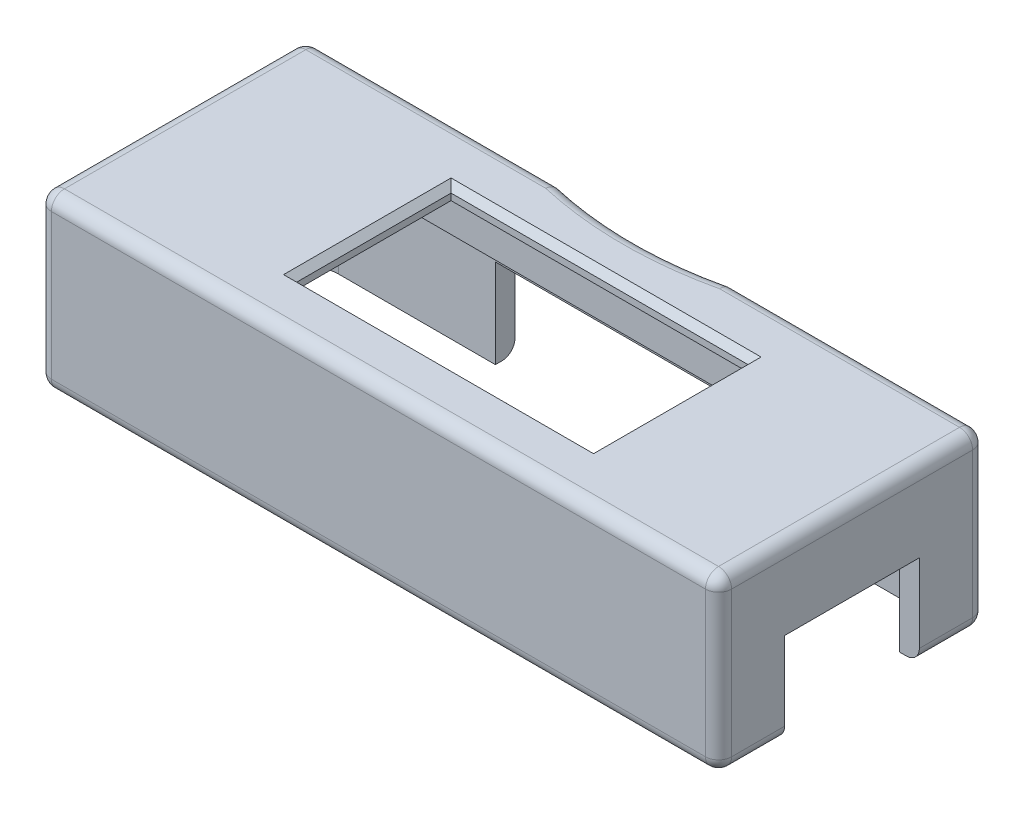
SolidWorks part; units mm, degrees
ref_plane "前视基准面" through (0, 0, 0) normal (0, 0, 1) x (1, 0, 0)
ref_plane "上视基准面" through (0, 0, 0) normal (0, 1, 0) x (1, 0, 0)
ref_plane "右视基准面" through (0, 0, 0) normal (1, 0, 0) x (0, 0, -1)
sketch "草图2" plane through (0, 0, 0) normal (0, 1, 0) x (1, 0, 0)
  line L0 (0.0138, 20.4331) -> (0, 0)
  line L1 (0.0138, 20.4331) -> (51.9961, 20.4188)
  line L2 (0, 0) -> (51.9944, 0)
  line L3 (51.9944, 0) -> (51.9961, 20.4188)
extrude "凸台-拉伸1" add sketch "草图2" along normal blind 13.1
sketch "草图3" plane through (0, 13.1, 0) normal (0, 1, 0) x (1, 0, 0)
  line L0 (15.5542, 4.1931) -> (38.2542, 4.1881)
  line L1 (15.5569, 15.9931) -> (38.2569, 15.9881)
  line L2 (38.2569, 15.9881) -> (38.2542, 4.1881)
  line L3 (15.5569, 15.9931) -> (15.5542, 4.1931)
extrude "切除-拉伸1" cut sketch "草图3" against normal blind 1
sketch "草图4" plane through (0, 12.1, 0) normal (0, 1, 0) x (1, 0, 0)
  line L0 (11.267, 17.1004) -> (39.707, 17.1016)
  line L1 (39.707, 17.1016) -> (39.704, 3.0812)
  line L2 (39.704, 3.0812) -> (11.264, 3.0877)
  line L3 (11.264, 3.0877) -> (11.267, 17.1004)
extrude "切除-拉伸2" cut sketch "草图4" against normal blind 3.5
sketch "草图6" plane through (0, 8.6, 0) normal (0, 1, 0) x (1, 0, 0)
  line L0 (4.0195, 18.932) -> (47.9974, 18.9199)
  line L1 (50.4968, 16.4194) -> (50.494, 3.9994)
  line L2 (47.9934, 1.5) -> (3.9935, 1.5)
  line L3 (1.4941, 4.0006) -> (1.5189, 16.4325)
  arc A0 (4.0195, 18.932) -> (1.5189, 16.4325) centre (4.0189, 16.432) ccw
  arc A1 (1.4941, 4.0006) -> (3.9935, 1.5) centre (3.9941, 4) ccw
  arc A2 (50.4968, 16.4194) -> (47.9974, 18.9199) centre (47.9968, 16.4199) ccw
  arc A3 (47.9934, 1.5) -> (50.494, 3.9994) centre (47.994, 4) ccw
extrude "切除-拉伸3" cut sketch "草图6" against normal blind 11.5
sketch "草图7" plane through (0, 8.6, 0) normal (0, 1, 0) x (1, 0, 0)
  circle A0 centre (4.987, 16.7698) radius 1.2
  circle A1 centre (4.984, 3.6578) radius 1.2
  circle A2 centre (44.9869, 16.7607) radius 1.2
  circle A3 centre (44.9839, 3.6487) radius 1.2
  dimension "D1" = 2.4
  dimension "D2" = 2.4
  dimension "D3" = 2.4
  dimension "D4" = 2.4
extrude "切除-拉伸4" cut sketch "草图7" along normal blind 3
sketch "草图15" plane through (0, 0, 0) normal (-1, 0, -0.0007) x (-0.0007, 0, 1)
  line L0 (-5.54, 3.59) -> (-10.21, 3.59)
  line L1 (-5.54, 7.2) -> (-5.54, 3.59)
  line L2 (-14.88, 3.59) -> (-10.21, 3.59)
  line L3 (-14.88, 7.2) -> (-14.88, 3.59)
  line L4 (-5.54, 7.2) -> (-14.88, 7.2)
  line L5 (-20.4331, 13.1) -> (0, 13.1) construction
  dimension "D1" = 5.9
extrude "切除-拉伸5" cut sketch "草图15" against normal blind 3
sketch "草图17" plane through (50.4931, 0, 0.0116) normal (-1, 0, -0.0002) x (-0.0002, 0, 1)
  line L0 (-5.06, 7) -> (-5.06, 0)
  line L1 (-15.36, 7) -> (-15.36, 0)
  line L2 (-5.06, 0) -> (-15.36, 0)
  line L3 (-5.06, 7) -> (-15.36, 7)
  line L4 (-20.4331, 13.1) -> (0, 13.1) construction
  line L5 (-20.4331, 0) -> (0, 0) construction
  dimension "D1" = 6.1
  dimension "D2" = 0
extrude "切除-拉伸7" cut sketch "草图17" against normal blind 3
sketch "草图23" plane through (0, 13.1, 0) normal (0, 1, 0) x (1, 0, 0)
  circle A0 centre (26.0152, 48.5808) radius 28.9053
extrude "切除-拉伸16" cut sketch "草图23" against normal blind 15
fillet "圆角1" radius 1 6 edges at (0.0069, 13.1, -10.2165) (25.9972, 13.1, 0) (51.9952, 13.1, -10.2094) (42.2737, 13.1, -20.4215) (26.0073, 13.1, -19.6755) (9.7388, 13.1, -20.4304)
fillet "圆角2" radius 1 8 edges at (51.7032, 12.8071, -20.126) (51.7015, 12.8071, -0.2929) (0.2931, 12.8071, -0.2929) (0.3065, 12.8071, -20.1401) (51.9961, 6.05, -20.4188) (51.9944, 6.05, 0) (0, 6.05, 0) (0.0138, 6.05, -20.4331)
chamfer "倒角1" distance 0.5 angle 45 4 edges at (15.5556, 13.1, -10.0931) (26.9042, 13.1, -4.1906) (38.2556, 13.1, -10.0881) (26.9069, 13.1, -15.9906)
fillet "圆角3" radius 1 11 edges at (51.9958, 0, -17.3835) (51.7032, 0, -20.1261) (10.2386, 0, -20.4303) (0.3063, 0, -20.1402) (0.0069, 0, -10.2171) (0.2933, 0, -0.2931) (51.9946, 0, -3.024) (51.7016, 0, -0.2929) (41.7738, 0, -20.4216) (26.0073, 0, -19.6755) (25.9976, 0, 0)
sketch "草图24" plane through (0, 8.6, 0) normal (0, 1, 0) x (1, 0, 0)
  line L0 (7.3923, 17.8998) -> (9.533, 17.8998)
  line L1 (9.533, 17.8998) -> (9.533, 14.192)
  line L2 (9.533, 14.192) -> (7.3923, 14.192)
  line L3 (7.3923, 14.192) -> (7.3923, 17.8998)
extrude "切除-拉伸17" cut sketch "草图24" along normal blind 2
fillet "圆角4" radius 1 4 edges at (0.7629, 7.2, -14.8795) (0.7505, 7.2, -5.5395) (0.7505, 3.59, -5.5395) (0.7629, 3.59, -14.8795)
sketch "草图26" plane through (0, 12.1, 0) normal (0, 1, 0) x (1, 0, 0)
  line L0 (10.7669, 17.2503) -> (39.9069, 17.2516)
  line L1 (39.9069, 17.2516) -> (39.904, 2.9312)
  line L2 (39.904, 2.9312) -> (10.7637, 2.9377)
  line L3 (10.7637, 2.9377) -> (10.7669, 17.2503)
extrude "切除-拉伸18" cut sketch "草图26" against normal blind 7
sketch "草图27" plane through (0, 8.6, 0) normal (0, 1, 0) x (1, 0, 0)
  circle A0 centre (48.4567, 15.69) radius 1.5
  circle A1 centre (48.4542, 4.69) radius 1.5
extrude "切除-拉伸19" cut sketch "草图27" along normal blind 2
sketch "草图28" plane through (0, 0, 0) normal (0, 1, 0) x (1, 0, 0)
  line L0 (36.0088, 20.4232) -> (36.0084, 18.7232)
  line L1 (16.0088, 20.4287) -> (16.0084, 18.7287)
  line L2 (36.0088, 20.4232) -> (16.0088, 20.4287)
  line L3 (36.0084, 18.7232) -> (16.0084, 18.7287)
  point P0 (16.0088, 20.4286)
extrude "切除-拉伸20" cut sketch "草图28" along normal blind 6.8
